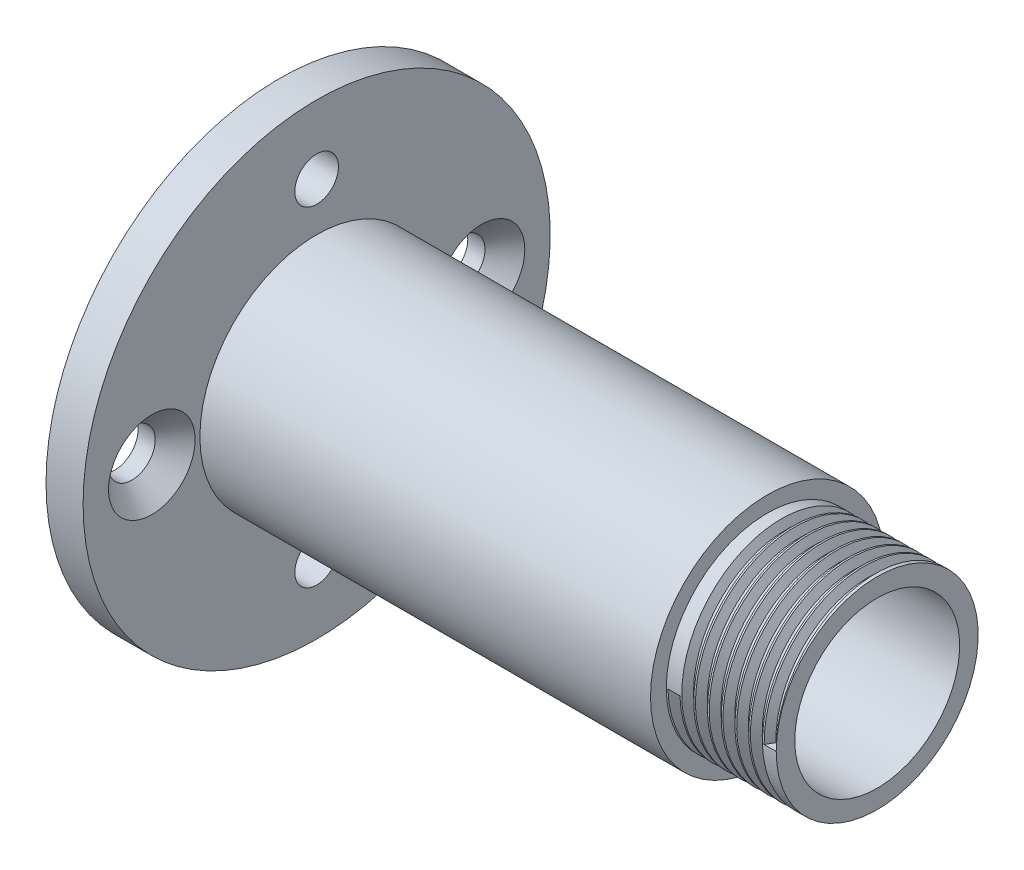
SolidWorks part; units mm, degrees
ref_plane "Front Plane" through (0, 0, 0) normal (0, 0, 1) x (1, 0, 0)
ref_plane "Top Plane" through (0, 0, 0) normal (0, 1, 0) x (1, 0, 0)
ref_plane "Right Plane" through (0, 0, 0) normal (1, 0, 0) x (0, 0, -1)
sketch "Sketch3" plane through (0, 0, 0) normal (0, 0, 1) x (1, 0, 0)
  line L0 (-58.5481, 189.9573) -> (284.033, 189.9573) construction
  line L2 (213.4012, -189.6279) -> (558.7345, -189.6279) construction
  line L4 (227.3705, -148.5737) -> (308.4812, -148.5737) construction
  line L41 (264.2584, -140.0737) -> (297.0584, -140.0737)
  line L42 (264.2584, -142.5737) -> (305.0584, -142.5737)
  line L43 (305.0584, -142.5737) -> (305.0584, -141.2237)
  line L44 (297.0584, -140.0737) -> (297.0584, -141.2237)
  line L45 (297.0584, -141.2237) -> (305.0584, -141.2237)
  line L48 (264.2584, -142.5737) -> (264.2584, -144.8237)
  line L55 (261.5584, -143.3237) -> (262.5584, -143.3237) construction
  line L56 (262.5584, -143.3237) -> (262.5584, -144.8237) construction
  line L58 (261.5584, -143.3237) -> (261.5584, -144.8237)
  line L59 (261.5584, -144.8237) -> (262.5584, -144.8237)
  line L61 (262.5584, -144.8237) -> (264.2584, -144.8237)
  line L94 (261.5584, -131.5737) -> (264.2584, -131.5737)
  line L97 (261.5584, -143.3237) -> (261.5584, -131.5737)
  line L112 (264.2584, -140.0737) -> (264.2584, -131.5737)
  dimension "D1" = 2.7
  dimension "D2" = 8
  dimension "D3" = 1.35
  dimension "D4" = 2.25
  dimension "D5" = 1.15
  dimension "D6" = 6
  dimension "D7" = 17
  dimension "D8" = 1.5
  dimension "D9" = 1
  dimension "D10" = 43.5
revolve "Revolve19" add sketch "Sketch3" angle 360 about L4
sketch "Sketch4" plane through (264.2584, 0, 0) normal (1, 0, 0) x (0, 0, -1)
  circle A0 centre (0, -148.5737) radius 12 construction
  circle A1 centre (0, -136.5737) radius 1.5875
  circle A2 centre (0, -160.5737) radius 1.5875
  dimension "D1" = 24
  dimension "D2" = 3.175
  dimension "D3" = 3.175
extrude "Cut-Extrude1" cut sketch "Sketch4" against normal up to next
hole_wizard "CSK for M3 Countersunk Flat Head Screw1" positions "Sketch11" profile "Sketch12" countersink size "M3" standard "ISO"
sketch "Sketch11" plane through (264.2584, 0, 0) normal (1, 0, 0) x (0, 0, -1)
  circle A1 centre (0, -148.5737) radius 12 construction
  point P12 (-12, -148.5737)
  point P14 (12, -148.5737)
sketch "Sketch12" plane through (264.2584, -148.5737, -12) normal (0, 1, 0) x (0, 0, -1)
  line L0 (0, 0) -> (0, 11.0215)
  line L1 (0, 11.0215) -> (1.7, 10)
  line L2 (1.7, 10) -> (1.7, 1.45)
  line L3 (1.7, 1.45) -> (3.15, 0)
  line L5 (3.15, 0) -> (0, 0)
  line L6 (-1.7, 1.45) -> (-3.15, 0) construction
  line L10 (0, 11.0215) -> (-1.7, 10) construction
  line L11 (0, -6.35) -> (0, 107.95) construction
  dimension "Hole Dia." = 3.4
  dimension "Hole Depth" = 10
  dimension "Near C'Sink Dia." = 6.3
  dimension "Near C'Sink Angle" = 90
  dimension "Drill Angle" = 118
sketch "Sketch13" plane through (261.5584, 0, 0) normal (-1, 0, 0) x (0, 0, 1)
  circle A0 centre (0, -148.5737) radius 6
  dimension "D1" = 12
extrude "Cut-Extrude2" cut sketch "Sketch13" against normal blind 1
sketch "Sketch14" plane through (262.5584, 0, 0) normal (-1, 0, 0) x (0, 0, 1)
  circle A0 centre (0, -148.5737) radius 6
extrude "Cut-Extrude3" cut sketch "Sketch14" against normal blind 10
thread "Thread1" pitch 1 start angle 0, offset 0, length 0, pitch 1, diameter 14.7
ref_plane "Plane1" through (305.0584, -148.5737, 7.35) normal (0, -1, 0) x (0, 0, 1)
sketch "Thread Profile1" plane through (305.0584, -148.5737, 7.35) normal (0, -1, 0) x (0, 0, 1)
  line L0 (0, 0) -> (0, 1) construction
  line L11 (0, 0) -> (0, 0.875)
  line L12 (0, 0.875) -> (-0.5413, 0.5625)
  line L13 (-0.5413, 0.5625) -> (-0.5413, 0.3125)
  line L15 (-0.5413, 0.3125) -> (0, 0)
  line L17 (-0.5413, 0.4375) -> (0, 0.4375) construction
  point P2 (0, 0)
  dimension "Pitch" = 1
  dimension "Profile_Angle" = 60
  dimension "Profile_Land" = 0.25
  dimension "Profile_Height" = 0.5413
